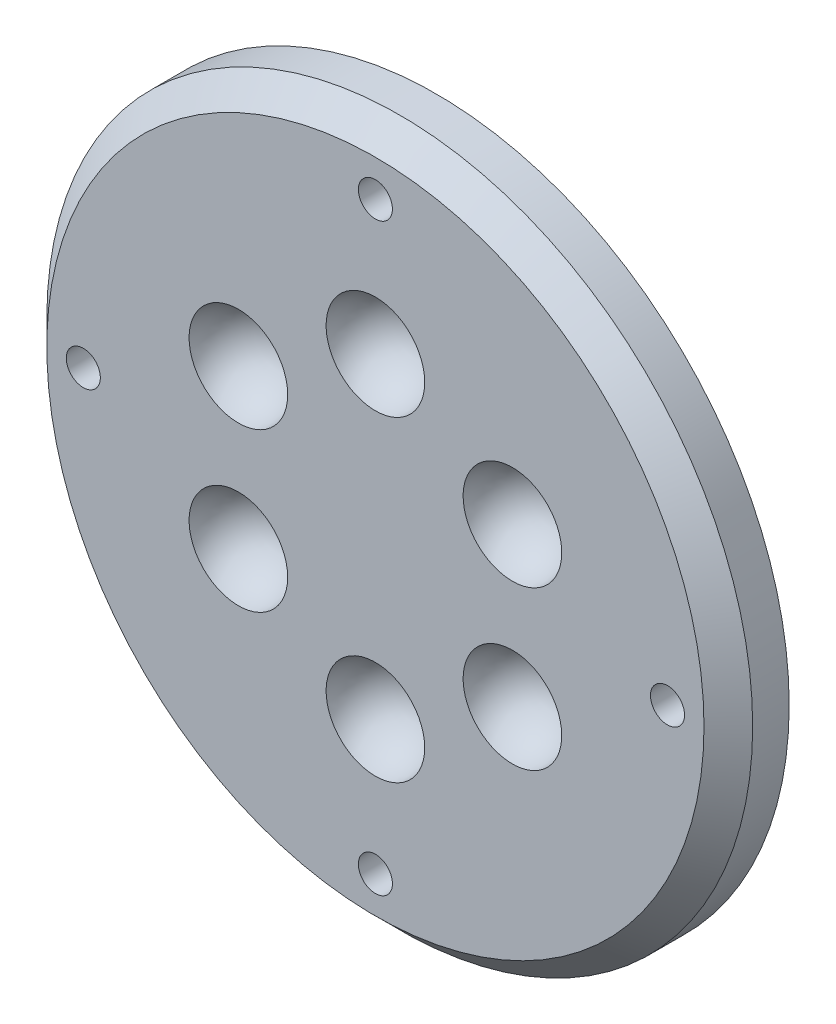
SolidWorks part; units mm, degrees
material "Copper"
ref_plane "Front Plane" through (0, 0, 0) normal (0, 0, 1) x (1, 0, 0)
ref_plane "Top Plane" through (0, 0, 0) normal (0, 1, 0) x (1, 0, 0)
ref_plane "Right Plane" through (0, 0, 0) normal (1, 0, 0) x (0, 0, -1)
sketch "Sketch1" plane through (0, 0, 0) normal (0, 0, 1) x (1, 0, 0)
  circle A0 centre (0, 0) radius 18.415
  dimension "D1" = 36.83
extrude "Boss-Extrude1" add sketch "Sketch1" along normal blind 3.175
sketch "Sketch2" plane through (0, 0, 3.175) normal (0, 0, 1) x (1, 0, 0)
  line L0 (0, 0) -> (0, 8.255)
  line L1 (0, 0) -> (7.149, 4.1275)
  line L2 (0, 0) -> (7.149, -4.1275)
  line L3 (0, 0) -> (0, -8.255)
  line L4 (0, 0) -> (-7.149, -4.1275)
  line L5 (0, 0) -> (-7.149, 4.1275)
  point P10 (0, 0)
  dimension "D1" = 8.255
  dimension "D2" = 6
ref_plane "Plane1" through (0, 0, 0) normal (1, 0, 0) x (0, 0, -1)
sketch "Sketch3" plane through (0, 0, 0) normal (1, 0, 0) x (0, 0, -1)
  line L0 (-3.175, 8.255) -> (-3.429, 8.255) construction
  line L1 (-3.175, 0) -> (-3.175, 8.255) construction
  line L2 (-3.175, 18.415) -> (-3.175, -18.415) construction
  line L3 (-6.0134, 8.255) -> (-0.8445, 8.255) construction
  line L4 (-6.0134, 8.255) -> (-0.8445, 8.255)
  arc A0 (-0.8445, 8.255) -> (-6.0134, 8.255) centre (-3.429, 8.255) ccw
  dimension "D2" = 5.1689
  dimension "D1" = 0.254
revolve "Cut-Revolve1" cut sketch "Sketch3" angle 360 about L4
ref_axis "Axis1" through (0, 0, 3.175) along (0, 0, -1)
pattern_circular "CirPattern1" count 6 over 360 about axis through (0, 0, 3.175) along (0, 0, -1) of "Cut-Revolve1"
sketch "Sketch4" plane through (0, 0, 0) normal (0, 0, -1) x (-1, 0, 0)
  line L1 (-12.7, 12.7) -> (12.7, 12.7)
  line L2 (-12.7, 12.7) -> (-12.7, -12.7)
  line L3 (-12.7, -12.7) -> (12.7, -12.7)
  line L4 (12.7, 12.7) -> (12.7, -12.7)
  line L5 (-12.7, 12.7) -> (12.7, -12.7) construction
  line L6 (-12.7, -12.7) -> (12.7, 12.7) construction
  point P0 (0, 0)
  dimension "D1" = 25.4
sketch "Sketch5" plane through (0, 0, 0) normal (0, 0, -1) x (-1, 0, 0)
  line L0 (0, 0) -> (0, 15.24)
  line L1 (0, 0) -> (15.24, 0)
  line L2 (0, 0) -> (0, -15.24)
  line L3 (0, 0) -> (-15.24, 0)
  point P9 (0, 0)
  dimension "D1" = 15.24
  dimension "D2" = 4
hole_wizard "#2-56 Tapped Hole1" positions "Sketch7" profile "Sketch8" tap size "#2-56" standard "ANSI Inch" end condition through all
sketch "Sketch7" plane through (0, 0, 0) normal (0, 0, -1) x (-1, 0, 0)
  point P0 (0, 15.24)
  point P3 (15.24, 0)
  point P6 (0, -15.24)
  point P9 (-15.24, 0)
sketch "Sketch8" plane through (0, 15.24, 0) normal (1, 0, 0) x (0, 1, 0)
  line L0 (0, 0) -> (0, 3.175)
  line L1 (0, 3.175) -> (0.889, 3.175)
  line L2 (0.889, 3.175) -> (0.889, 0)
  line L5 (0.889, 0) -> (0, 0)
  line L11 (0, -6.35) -> (0, 107.95) construction
  dimension "Thru Tap Drill Dia." = 1.778
  dimension "Thru Tap Drill Depth" = 3.175
cosmetic thread "Hole Thread1" parameters "D2"=2.1844
cosmetic thread "Hole Thread2" parameters "D2"=2.1844
cosmetic thread "Hole Thread3" parameters "D2"=2.1844
cosmetic thread "Hole Thread4" parameters "D2"=2.1844
chamfer "Chamfer1" distance 1.27 angle 45 1 edges at (18.415, 0, 3.175)
